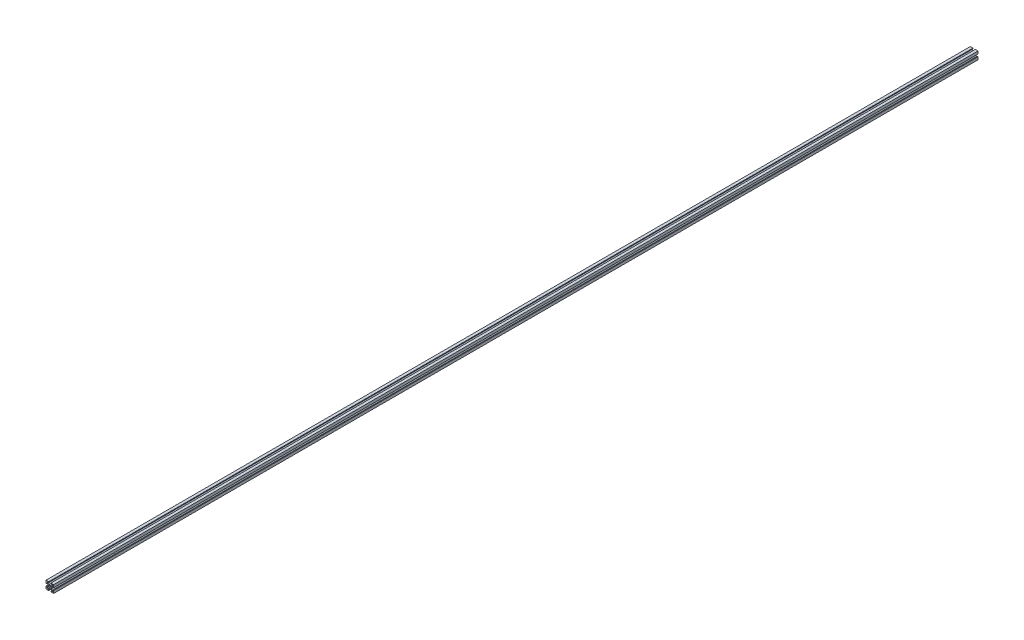
SolidWorks part; units mm, degrees
ref_plane "Front Plane" through (0, 0, 0) normal (0, 0, 1) x (1, 0, 0)
ref_plane "Top Plane" through (0, 0, 0) normal (0, 1, 0) x (1, 0, 0)
ref_plane "Right Plane" through (0, 0, 0) normal (1, 0, 0) x (0, 0, -1)
sketch "Esquisse2" plane through (0, 0, 0) normal (0, 0, 1) x (1, 0, 0)
  line L0 (-1, -2) -> (1, -2)
  line L1 (1, -2) -> (3.3835, -4)
  line L2 (3.3835, -4) -> (1.5, -4)
  line L3 (1.5, -4) -> (1.5, -5)
  line L4 (1.5, -5) -> (5, -5)
  line L5 (-1, -2) -> (-3.3835, -4)
  line L6 (-3.3835, -4) -> (-1.5, -4)
  line L7 (-1.5, -4) -> (-1.5, -5)
  line L8 (-1.5, -5) -> (-5, -5)
  line L9 (-5, -5) -> (-5, -1.5)
  line L10 (-5, -1.5) -> (-4, -1.5)
  line L11 (-4, -1.5) -> (-4, -3.3835)
  line L12 (-4, -3.3835) -> (-2, -1)
  line L13 (-2, -1) -> (-2, 1)
  line L14 (-2, 1) -> (-4, 3.3835)
  line L15 (-4, 3.3835) -> (-4, 1.5)
  line L16 (-4, 1.5) -> (-5, 1.5)
  line L17 (-5, 1.5) -> (-5, 5)
  line L18 (-5, 5) -> (-1.5, 5)
  line L19 (-1.5, 5) -> (-1.5, 4)
  line L20 (-1.5, 4) -> (-3.3835, 4)
  line L21 (-3.3835, 4) -> (-1, 2)
  line L22 (-1, 2) -> (1, 2)
  line L23 (1, 2) -> (3.3835, 4)
  line L24 (3.3835, 4) -> (1.5, 4)
  line L25 (1.5, 4) -> (1.5, 5)
  line L26 (1.5, 5) -> (5, 5)
  line L27 (5, 5) -> (5, 1.5)
  line L28 (5, 1.5) -> (4, 1.5)
  line L29 (4, 1.5) -> (4, 3.3835)
  line L30 (4, 3.3835) -> (2, 1)
  line L31 (2, -1) -> (2, 1)
  line L32 (2, -1) -> (4, -3.3835)
  line L33 (4, -3.3835) -> (4, -1.5)
  line L34 (4, -1.5) -> (5, -1.5)
  line L35 (5, -1.5) -> (5, -5)
  circle A0 centre (0, 0) radius 1.25
  point P4 (0, -2)
  point P34 (0, 2)
  point P40 (2, 0)
  dimension "D4" = 2.5
  dimension "D1" = 2
  dimension "D2" = 3.5
  dimension "D3" = 1
  dimension "D5" = 10
  dimension "D6" = 10
  dimension "D7" = 140
  dimension "D8" = 4
  dimension "D9" = 4
  dimension "D10" = 3.5
  dimension "D11" = 3
extrude "Main Extrusion" add sketch "Esquisse2" along normal blind 1200
